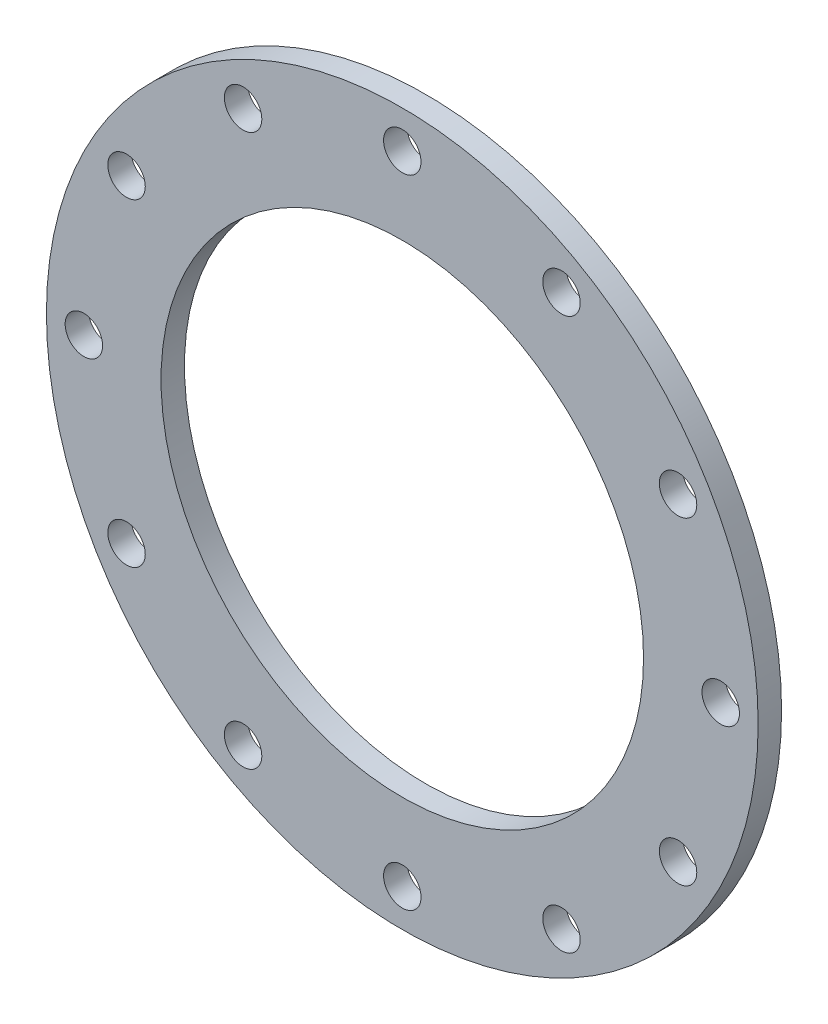
SolidWorks part; units mm, degrees
material "Ductile Iron"
ref_plane "Front Plane" through (0, 0, 0) normal (0, 0, 1) x (1, 0, 0)
ref_plane "Top Plane" through (0, 0, 0) normal (0, 1, 0) x (1, 0, 0)
ref_plane "Right Plane" through (0, 0, 0) normal (1, 0, 0) x (0, 0, -1)
sketch "Profile Sketch" plane through (0, 0, 0) normal (0, 0, 1) x (1, 0, 0)
  circle A0 centre (0, 0) radius 241.3
  circle A1 centre (0, 0) radius 163.576
  circle A2 centre (0, 0) radius 215.9 construction
  circle A3 centre (0, 215.9) radius 12.7
  circle A4 centre (107.95, 186.9749) radius 12.7
  circle A5 centre (186.9749, 107.95) radius 12.7
  circle A6 centre (215.9, 0) radius 12.7
  circle A7 centre (186.9749, -107.95) radius 12.7
  circle A8 centre (107.95, -186.9749) radius 12.7
  circle A9 centre (0, -215.9) radius 12.7
  circle A10 centre (-107.95, -186.9749) radius 12.7
  circle A11 centre (-186.9749, -107.95) radius 12.7
  circle A12 centre (-215.9, 0) radius 12.7
  circle A13 centre (-186.9749, 107.95) radius 12.7
  circle A14 centre (-107.95, 186.9749) radius 12.7
  point P31 (0, 0)
  dimension "D1" = 327.152
  dimension "D2" = 482.6
  dimension "D3" = 431.8
  dimension "D4" = 25.4
  dimension "D5" = 12
extrude "Boss-Extrude1" add sketch "Profile Sketch" along normal blind 15.875
equation "\"ID\"= 12.88in'RJSALES"
equation "\"BC\"= 17in'RJSALES"
equation "\"OD\"= 19in'RJSALES"
equation "\"HD\"= 1in'RJSALES"
equation "\"T\"= 0.625in'RJSALES"
equation "\"D1@Profile Sketch\" = \"ID\""
equation "\"D2@Profile Sketch\" = \"OD\""
equation "\"D3@Profile Sketch\" = \"BC\""
equation "\"D4@Profile Sketch\" = \"HD\""
equation "\"D1@Boss-Extrude1\"=\"T\""
